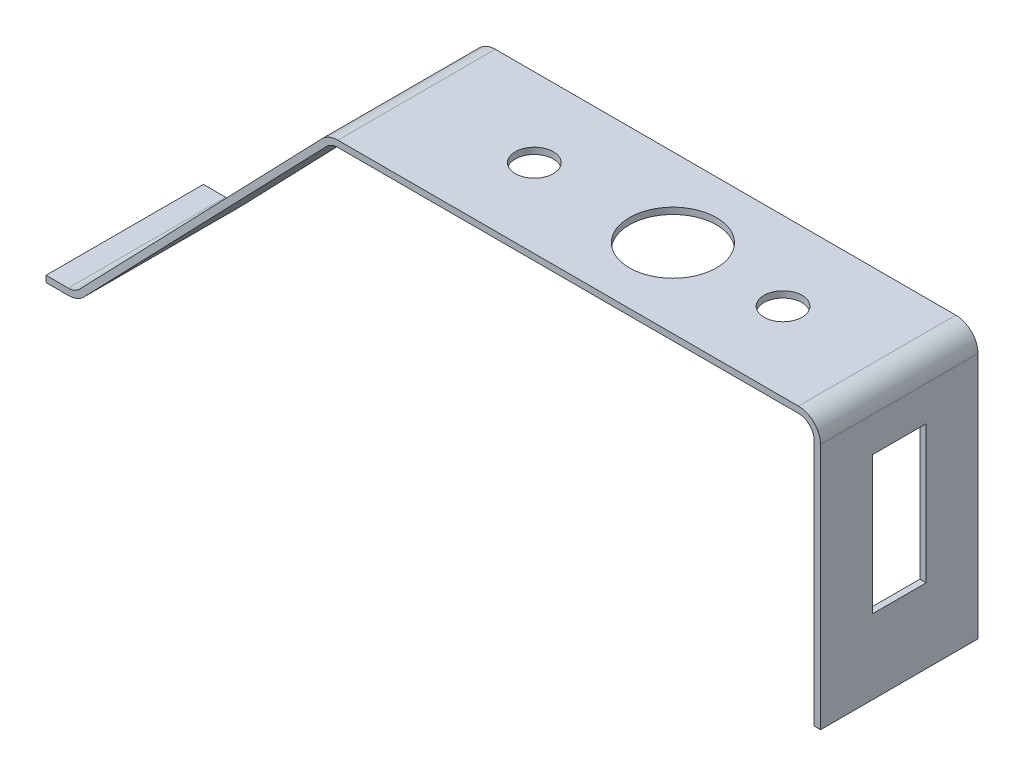
SolidWorks part; units mm, degrees
material "Plain Carbon Steel"
ref_plane "Front Plane" through (0, 0, 0) normal (0, 0, 1) x (1, 0, 0)
ref_plane "Top Plane" through (0, 0, 0) normal (0, 1, 0) x (1, 0, 0)
ref_plane "Right Plane" through (0, 0, 0) normal (1, 0, 0) x (0, 0, -1)
ref_axis "X-axis" through (-88.99, 0, 0) along (1, 0, 0)
ref_axis "Y-axis" through (0, -55, 0) along (0, 1, 0)
ref_axis "Z-axis" through (0, 0, 55) along (0, 0, -1)
sketch "Sketch1" plane through (0, 0, 0) normal (0, 0, 1) x (1, 0, 0)
  line L0 (0, 0) -> (2.54, 0)
  line L1 (2.54, 0) -> (22.86, 21.082)
  line L2 (22.86, 21.082) -> (61.595, 21.082)
  line L3 (61.595, 21.082) -> (61.595, 0)
  dimension "D1" = 21.082
  dimension "D2" = 38.735
  dimension "D3" = 59.055
  dimension "D4" = 2.54
extrude "Extrude-Thin1" add sketch "Sketch1" along normal mid plane 12.6238 thin thin type one direction reverse wall 0.508
sketch "Sketch2" plane through (62.103, 0, 0) normal (1, 0, 0) x (0, 0, -1)
  line L0 (-6.3119, 0) -> (6.3119, 0) construction
  line L1 (-2.159, 17.018) -> (2.159, 17.018)
  line L2 (-2.159, 17.018) -> (-2.159, 5.969)
  line L3 (-2.159, 5.969) -> (2.159, 5.969)
  line L4 (2.159, 17.018) -> (2.159, 5.969)
  line L5 (-2.159, 17.018) -> (2.159, 5.969) construction
  line L6 (-2.159, 5.969) -> (2.159, 17.018) construction
  line L7 (0, -2.9767) -> (0, 25.9483) construction
  point P0 (0, 11.4935)
  dimension "D1" = 5.969
  dimension "D2" = 11.049
  dimension "D3" = 4.318
extrude "Cut-Extrude1" cut sketch "Sketch2" against normal up to next
sketch "Sketch3" plane through (0, 21.59, 0) normal (0, 1, 0) x (1, 0, 0)
  line L0 (62.103, -6.3119) -> (62.103, 6.3119) construction
  line L1 (67.9253, 0) -> (-4.3088, 0) construction
  circle A0 centre (52.7812, 0) radius 1.524
  circle A1 centre (32.8422, 0) radius 1.524
  circle A2 centre (43.9547, 0) radius 3.4925
  dimension "D2" = 3.048
  dimension "D3" = 19.939
  dimension "D4" = 6.985
  dimension "D5" = 6.096
  dimension "D1" = 7.7978
extrude "Cut-Extrude2" cut sketch "Sketch3" against normal up to next
